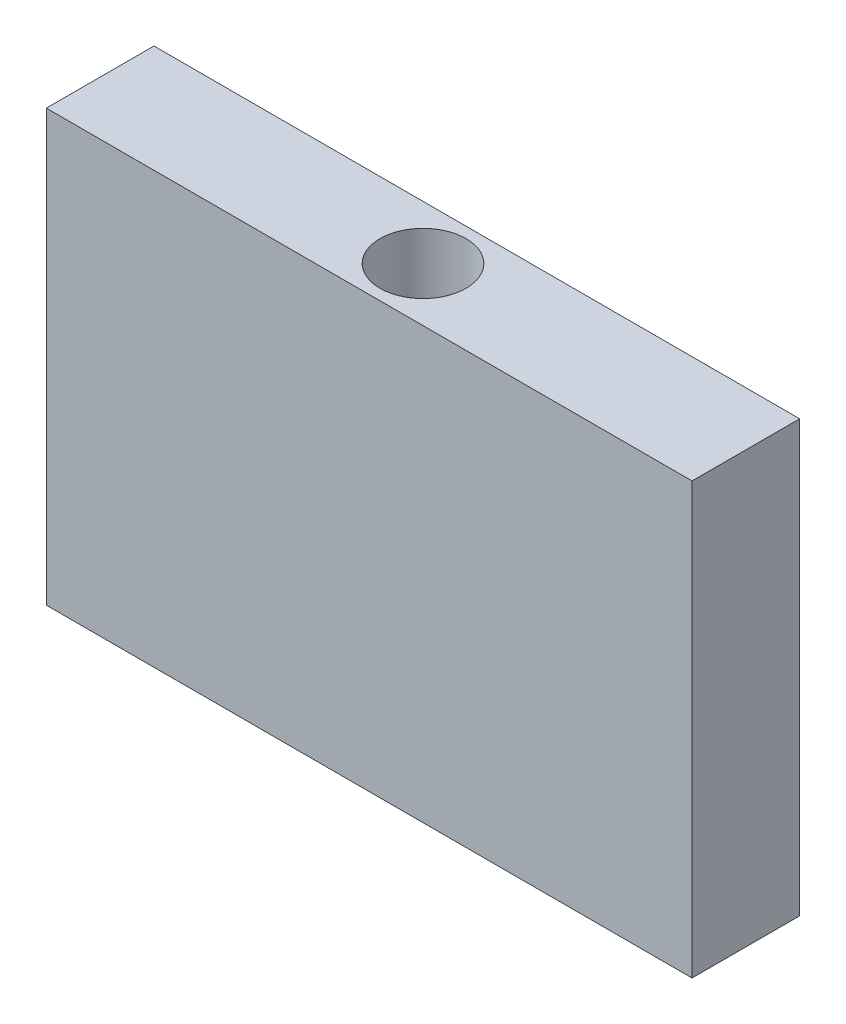
SolidWorks part; units mm, degrees
ref_plane "Front Plane" through (0, 0, 0) normal (0, 0, 1) x (1, 0, 0)
ref_plane "Top Plane" through (0, 0, 0) normal (0, 1, 0) x (1, 0, 0)
ref_plane "Right Plane" through (0, 0, 0) normal (1, 0, 0) x (0, 0, -1)
sketch "Sketch2" plane through (0, 0, 0) normal (0, 1, 0) x (1, 0, 0)
  line L1 (-30, -5) -> (30, -5)
  line L2 (-30, -5) -> (-30, 5)
  line L3 (-30, 5) -> (30, 5)
  line L4 (30, -5) -> (30, 5)
  line L5 (-30, -5) -> (30, 5) construction
  line L6 (-30, 5) -> (30, -5) construction
  circle A0 centre (0, 0) radius 4
  point P0 (0, 0)
  dimension "D3" = 8
  dimension "D1" = 60
  dimension "D2" = 10
extrude "Boss-Extrude1" add sketch "Sketch2" along normal blind 40
sketch "Sketch5" plane through (0, 0, 5) normal (0, 0, 1) x (1, 0, 0)
  line L0 (0, 40) -> (0, 0) construction
  line L1 (-30, 40) -> (30, 40) construction
  line L2 (-30, 20) -> (30, 20) construction
  line L3 (-30, 40) -> (-30, 0) construction
  line L4 (10, -976.9914) -> (10, 49023.0086)
  line L5 (13, -975.6958) -> (13, 49024.3042) construction
  line L6 (-1016.8946, 25) -> (48983.1054, 25)
  line L7 (30, 40) -> (30, 0) construction
  dimension "D1" = 10
  dimension "D2" = 3
  dimension "D3" = 5
sketch "Sketch6" plane through (0, 0, 5) normal (0, 0, 1) x (1, 0, 0)
  line L0 (-201016.8946, 25) -> (248983.1054, 25) construction
  line L1 (13, -200975.6958) -> (13, 249024.3042) construction
  line L2 (0, 40) -> (0, 0) construction
  line L3 (-30, 0) -> (30, 0) construction
  line L4 (-30, 20) -> (30, 20) construction
  circle A0 centre (17, 29) radius 4
  circle A1 centre (17, 29) radius 1.5
  circle A2 centre (-17, 29) radius 1.5
  circle A3 centre (-17, 29) radius 4
  circle A4 centre (17, 11) radius 1.5
  circle A5 centre (17, 11) radius 4
  circle A6 centre (-17, 11) radius 1.5
  circle A7 centre (-17, 11) radius 4
  point P20 (-30, 20)
  dimension "D1" = 8
  dimension "D2" = 3
sketch "Sketch7" plane through (0, 40, 0) normal (0, 1, 0) x (1, 0, 0)
extrude "Boss-Extrude2" add sketch "Sketch2<2>" along normal blind 25.5
sketch "Sketch2<2>" plane through (0, 0, 0) normal (0, 1, 0) x (1, 0, 0) same geometry as "Sketch2"
sketch "Sketch8" plane through (0, 40, 0) normal (0, 1, 0) x (1, 0, 0)
  line L0 (0, 0) -> (0, 8.3294) construction
